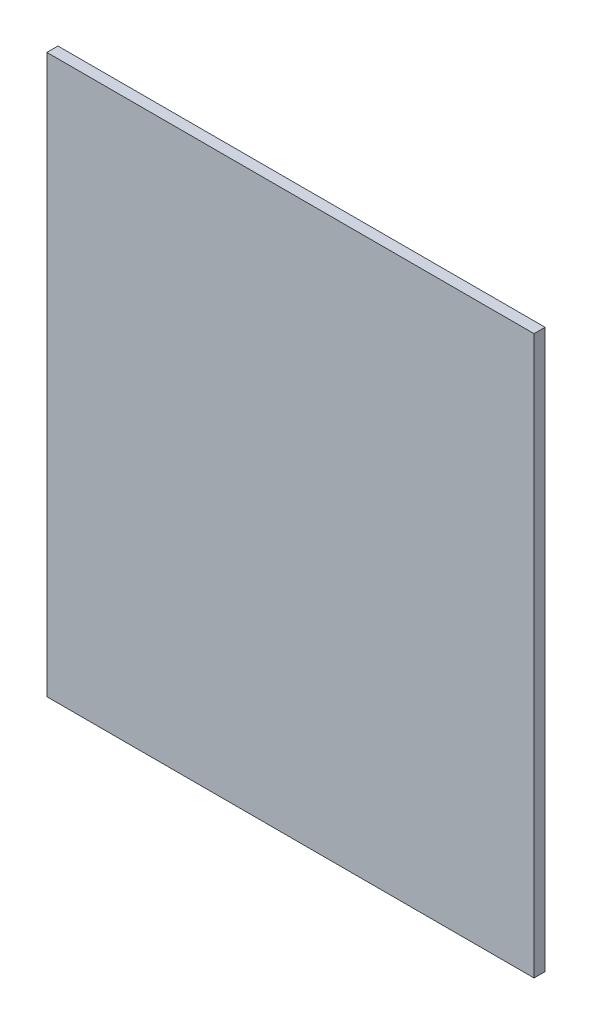
SolidWorks part; units mm, degrees
material "ABS PC"
ref_plane "Plan de face" through (0, 0, 0) normal (0, 0, 1) x (1, 0, 0)
ref_plane "Plan de dessus" through (0, 0, 0) normal (0, 1, 0) x (1, 0, 0)
ref_plane "Plan de droite" through (0, 0, 0) normal (1, 0, 0) x (0, 0, -1)
sketch "Esquisse1" plane through (0, 0, 0) normal (0, 0, 1) x (1, 0, 0)
  line L1 (130, 31.2) -> (350, 31.2)
  line L2 (130, 31.2) -> (130, -220.8)
  line L3 (130, -220.8) -> (350, -220.8)
  line L4 (350, 31.2) -> (350, -220.8)
  line L5 (337, 31.2) -> (7, 31.2) construction
  line L6 (337, -220.8) -> (65.8, -220.8) construction
  line L7 (350, 23.2) -> (350, -222.0619) construction
extrude "Boss.-Extru.1" add sketch "Esquisse1" along normal blind 5
